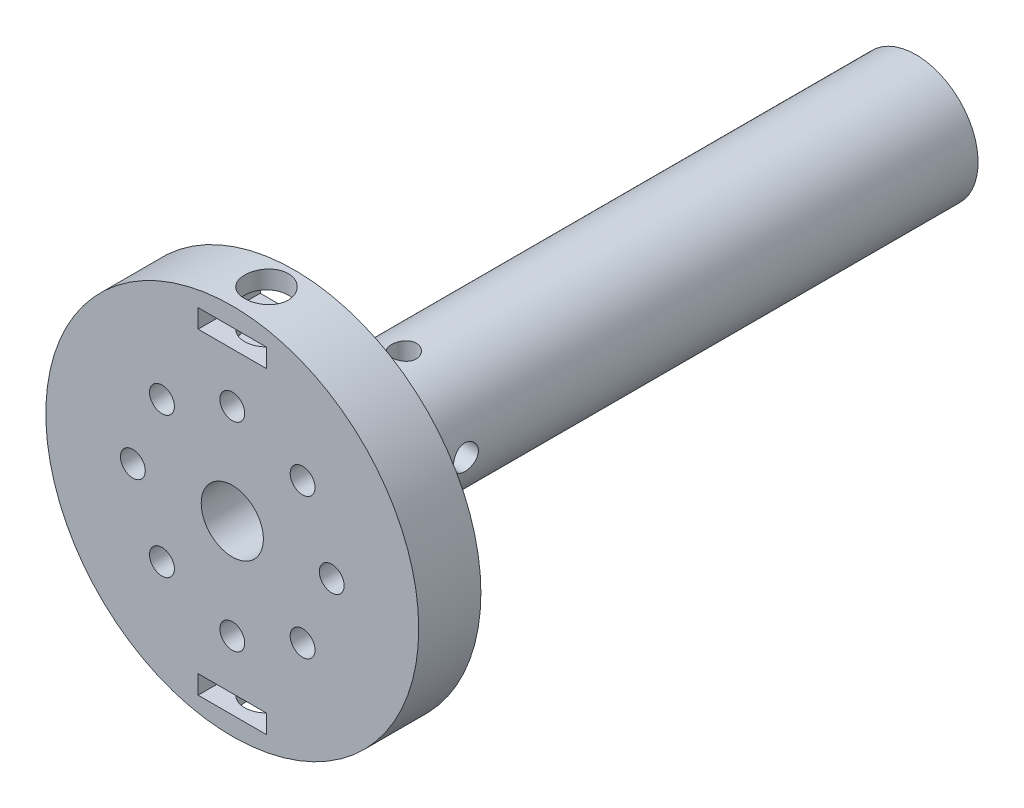
SolidWorks part; units mm, degrees
ref_plane "Front Plane" through (0, 0, 0) normal (0, 0, 1) x (1, 0, 0)
ref_plane "Top Plane" through (0, 0, 0) normal (0, 1, 0) x (1, 0, 0)
ref_plane "Right Plane" through (0, 0, 0) normal (1, 0, 0) x (0, 0, -1)
sketch "Sketch1" plane through (0, 0, 0) normal (0, 0, 1) x (1, 0, 0)
  circle A0 centre (0, 0) radius 30
  dimension "D1" = 60
extrude "Boss-Extrude1" add sketch "Sketch1" along normal blind 10
sketch "Sketch2" plane through (0, 0, 0) normal (0, 0, -1) x (-1, 0, 0)
  circle A0 centre (0, 0) radius 10
  dimension "D1" = 20
extrude "Boss-Extrude2" add sketch "Sketch2" along normal blind 100
extrude "Boss-Extrude3" add sketch "Sketch2<2>" along normal blind 20
sketch "Sketch2<2>" plane through (0, 0, 0) normal (0, 0, -1) x (-1, 0, 0) same geometry as "Sketch2"
sketch "Sketch5" plane through (0, 0, -100) normal (0, 0, -1) x (-1, 0, 0)
  circle A0 centre (0, 0) radius 5
  dimension "D1" = 10
extrude "Cut-Extrude1" cut sketch "Sketch5" against normal through all
sketch "Sketch6" plane through (0, 0, 0) normal (0, 1, 0) x (1, 0, 0)
  line L1 (30, 0) -> (-30, 0) construction
  circle A0 centre (0, 17.6) radius 2
  dimension "D1" = 4
  dimension "D2" = 17.6
extrude "Cut-Extrude2" cut sketch "Sketch6" against normal through all both and the other way through all
pattern_circular "CirPattern1" count 2 every 90 about axis through (0, 0, -100) along (0, 0, 1) of "Cut-Extrude2"
sketch "Sketch7" plane through (0, 0, 10) normal (0, 0, 1) x (1, 0, 0)
  circle A0 centre (0, 16) radius 2
  circle A1 centre (11.3137, 11.3137) radius 2
  circle A2 centre (16, 0) radius 2
  circle A3 centre (11.3137, -11.3137) radius 2
  circle A4 centre (0, -16) radius 2
  circle A5 centre (-11.3137, -11.3137) radius 2
  circle A6 centre (-16, 0) radius 2
  circle A7 centre (-11.3137, 11.3137) radius 2
  point P20 (0, 0)
  dimension "D1" = 4
  dimension "D2" = 16
  dimension "D3" = 8
extrude "Cut-Extrude3" cut sketch "Sketch7" against normal through all and the other way through all
sketch "Sketch9" plane through (0, 0, 0) normal (0, 0, -1) x (-1, 0, 0)
  line L0 (0, 0) -> (0, 30) construction
  line L3 (-5.5, 24) -> (5.5, 24)
  line L4 (-5.5, 24) -> (-5.5, 27)
  line L5 (-5.5, 27) -> (5.5, 27)
  line L6 (5.5, 24) -> (5.5, 27)
  line L7 (-5.5, 24) -> (5.5, 27) construction
  line L8 (-5.5, 27) -> (5.5, 24) construction
  circle A0 centre (0, 0) radius 30 construction
  point P6 (0, 25.5)
  dimension "D1" = 11
  dimension "D2" = 3
  dimension "D3" = 24
extrude "Cut-Extrude5" cut sketch "Sketch9" against normal blind 10
mirror "Mirror1" about plane through (0, 0, 0) normal (0, 1, 0) of "Cut-Extrude5"
ref_plane "Plane1" through (0, -30, 0) normal (0, -1, 0) x (-1, 0, 0)
sketch "Sketch10" plane through (0, -30, 0) normal (0, -1, 0) x (-1, 0, 0)
  line L1 (0, -1) -> (1.1394, -1) construction
  line L2 (30, 0) -> (-30, 0) construction
  circle A0 centre (0, -4.5) radius 3.5
  dimension "D1" = 7
  dimension "D2" = 1
  dimension "D3" = 3.5
extrude "Cut-Extrude6" cut sketch "Sketch10" against normal blind 8
mirror "Mirror2" about plane through (0, 0, 0) normal (0, 1, 0) of "Cut-Extrude6"
sketch "Sketch15" plane through (0, 0, 0) normal (0, 1, 0) x (1, 0, 0)
  line L0 (-30.0139, 75) -> (35.3147, 75) construction
  line L1 (10, 100) -> (-10, 100) construction
  dimension "D1" = 25
ref_plane "Plane3" through (0, 0, -75) normal (0, 0, -1) x (-1, 0, 0)
sketch "Sketch17" plane through (0, 0, -75) normal (0, 0, -1) x (-1, 0, 0)
  circle A0 centre (0, 0) radius 7.3556
extrude "Boss-Extrude4" add sketch "Sketch17" along normal blind 25
sketch "Sketch18" plane through (0, 0, -100) normal (0, 0, -1) x (-1, 0, 0)
  circle A0 centre (0, 0) radius 3
  dimension "D1" = 6
extrude "Cut-Extrude7" cut sketch "Sketch18" against normal blind 15
sketch "Sketch19" plane through (0, 0, -85) normal (0, 0, -1) x (-1, 0, 0)
  line L0 (0, 0) -> (0, 2.5) construction
  line L1 (1.6583, 2.5) -> (-1.6583, 2.5)
  arc A0 (1.6583, 2.5) -> (-1.6583, 2.5) centre (0, 0) ccw
  dimension "D1" = 2.5
extrude "Boss-Extrude5" add sketch "Sketch19" along normal blind 10
